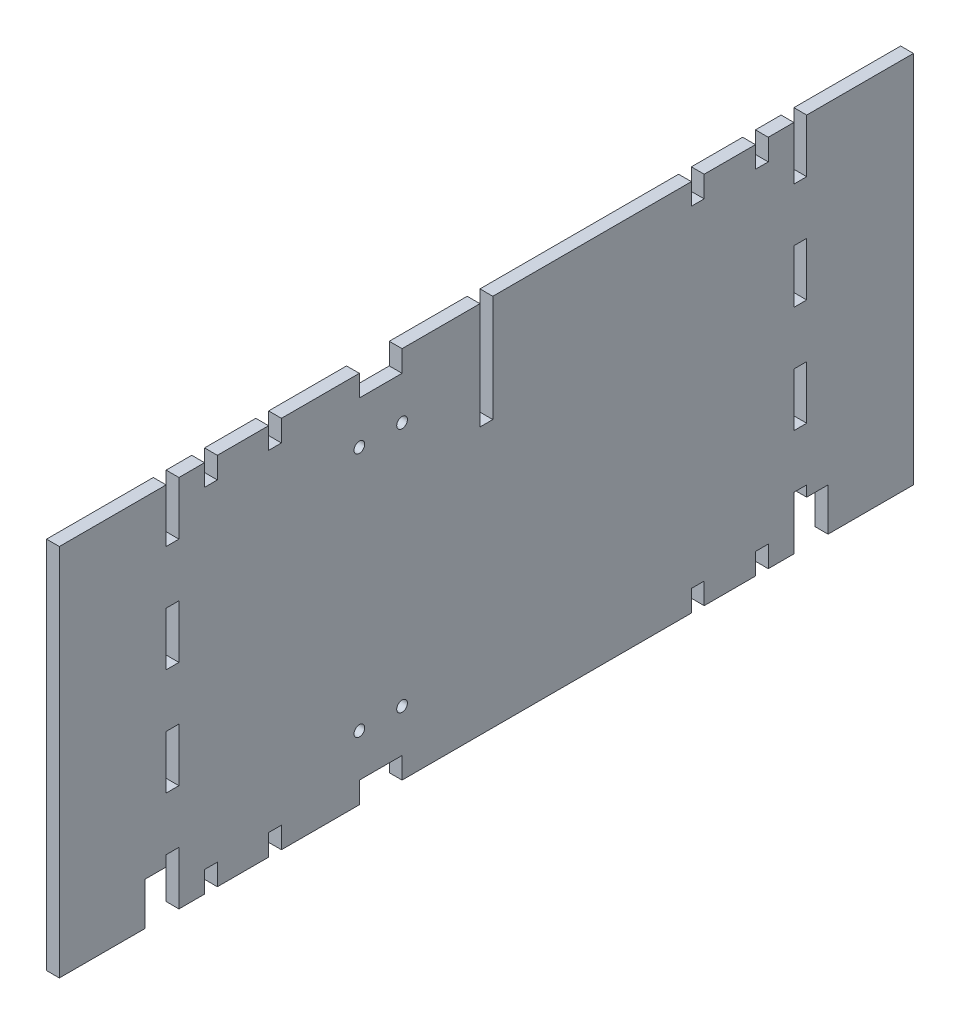
SolidWorks part; units mm, degrees
ref_plane "Front" through (0, 0, 0) normal (0, 0, 1) x (1, 0, 0)
ref_plane "Top" through (0, 0, 0) normal (0, 1, 0) x (1, 0, 0)
ref_plane "Right" through (0, 0, 0) normal (1, 0, 0) x (0, 0, -1)
sketch "Sketch1" plane through (0, 0, 0) normal (1, 0, 0) x (0, 0, -1)
  line L1 (0, 0) -> (-400, 0)
  line L2 (0, 0) -> (0, 175)
  line L3 (0, 175) -> (-400, 175)
  line L4 (-400, 0) -> (-400, 175)
  dimension "D1" = 400
  dimension "D2" = 175
extrude "Boss-Extrude1" add sketch "Sketch1" along normal blind 6
sketch "Sketch3" plane through (6, 0, 0) normal (1, 0, 0) x (0, 0, -1)
  line L0 (-400, 175) -> (-400, 0) construction
  line L1 (-350, 175) -> (-344, 175)
  line L2 (-350, 175) -> (-350, 150)
  line L3 (-350, 150) -> (-344, 150)
  line L4 (-344, 175) -> (-344, 150)
  line L5 (0, 175) -> (-400, 175) construction
  dimension "D1" = 6
  dimension "D2" = 25
  dimension "D3" = 50
extrude "Cut-Extrude1" cut sketch "Sketch3" against normal through all
pattern_linear "LPattern1" count 2 spacing 294 along (0, 0, -1) count 4 spacing 50 along (0, -1, 0) of "Cut-Extrude1"
sketch "Sketch4" plane through (6, 0, 0) normal (1, 0, 0) x (0, 0, -1)
  line L0 (-56, 175) -> (-344, 175) construction
  line L1 (-332, 175) -> (-326, 175)
  line L2 (-332, 175) -> (-332, 165)
  line L3 (-332, 165) -> (-326, 165)
  line L4 (-326, 175) -> (-326, 165)
  line L5 (-344, 150) -> (-344, 175) construction
  dimension "D1" = 6
  dimension "D2" = 12
  dimension "D3" = 10
extrude "Cut-Extrude2" cut sketch "Sketch4" against normal through all
pattern_linear "LPattern2" count 2 spacing 258 along (0, 0, -1) count 2 spacing 165 along (0, -1, 0) of "Cut-Extrude2"
sketch "Sketch5" plane through (6, 0, 0) normal (1, 0, 0) x (0, 0, -1)
  line L0 (-74, 175) -> (-326, 175) construction
  line L1 (-302, 175) -> (-296, 175)
  line L2 (-302, 175) -> (-302, 165)
  line L3 (-302, 165) -> (-296, 165)
  line L4 (-296, 175) -> (-296, 165)
  line L5 (-326, 165) -> (-326, 175) construction
  line L6 (-332, 165) -> (-326, 165) construction
  dimension "D1" = 24
  dimension "D2" = 6
extrude "Cut-Extrude3" cut sketch "Sketch5" against normal through all
pattern_linear "LPattern3" count 2 spacing 165 along (0, -1, 0) count 2 spacing 198 along (0, 0, -1) of "Cut-Extrude3"
sketch "Sketch6" plane through (6, 0, 0) normal (1, 0, 0) x (0, 0, -1)
  line L0 (-104, 175) -> (-296, 175) construction
  line L1 (-203, 175) -> (-197, 175)
  line L2 (-203, 175) -> (-203, 125)
  line L3 (-203, 125) -> (-197, 125)
  line L4 (-197, 175) -> (-197, 125)
  point P6 (-200, 175)
  point P7 (-200, 175)
  dimension "D1" = 6
  dimension "D2" = 50
extrude "Cut-Extrude4" cut sketch "Sketch6" against normal blind 10
sketch "Sketch7" plane through (6, 0, 0) normal (1, 0, 0) x (0, 0, -1)
  line L0 (-203, 175) -> (-296, 175) construction
  line L1 (-259.5, 175) -> (-239.5, 175)
  line L2 (-259.5, 175) -> (-259.5, 165)
  line L3 (-259.5, 165) -> (-239.5, 165)
  line L4 (-239.5, 175) -> (-239.5, 165)
  point P6 (-249.5, 175)
  point P7 (-249.5, 175)
  dimension "D1" = 10
  dimension "D2" = 20
extrude "Cut-Extrude5" cut sketch "Sketch7" against normal blind 10
pattern_linear "LPattern4" count 2 spacing 165 along (0, -1, 0) of "Cut-Extrude5"
sketch "Sketch8" plane through (6, 0, 0) normal (1, 0, 0) x (0, 0, -1)
  line L0 (-259.5, 145) -> (-239.5, 145) construction
  line L1 (-259.5, 30) -> (-239.5, 30) construction
  line L2 (-249.5, 165) -> (-249.5, 10) construction
  line L3 (-259.5, 165) -> (-239.5, 165) construction
  line L4 (-239.5, 10) -> (-259.5, 10) construction
  circle A0 centre (-259.5, 145) radius 2.5
  circle A1 centre (-239.5, 145) radius 2.5
  circle A2 centre (-259.5, 30) radius 2.5
  circle A3 centre (-239.5, 30) radius 2.5
  point P8 (-249.5, 145)
  point P15 (-249.5, 30)
  dimension "D3" = 5
  dimension "D1" = 20
  dimension "D2" = 20
  dimension "D4" = 20
extrude "Cut-Extrude6" cut sketch "Sketch8" against normal blind 10
sketch "Sketch9" plane through (6, 0, 0) normal (1, 0, 0) x (0, 0, -1)
  line L0 (-350, 25) -> (-350, 0) construction
  line L1 (-350, 20) -> (-360, 20)
  line L2 (-350, 20) -> (-350, 0)
  line L3 (-350, 0) -> (-360, 0)
  line L4 (-360, 20) -> (-360, 0)
  line L5 (-400, 0) -> (-350, 0) construction
  dimension "D1" = 10
  dimension "D2" = 20
extrude "Cut-Extrude7" cut sketch "Sketch9" against normal blind 10
pattern_linear "LPattern5" count 2 spacing 310 along (0, 0, -1) of "Cut-Extrude7"
equation "\"`10\"=11.8105"
